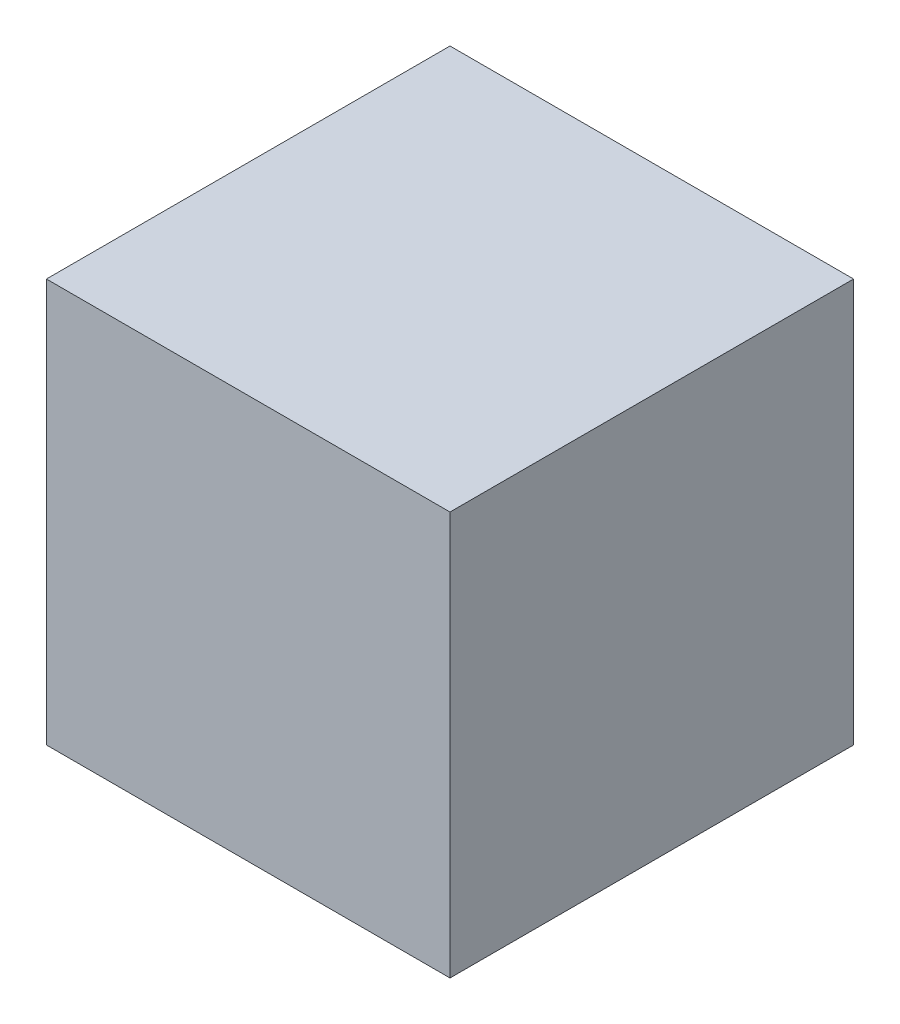
SolidWorks part; units mm, degrees
ref_plane "Front Plane" through (0, 0, 0) normal (0, 0, 1) x (1, 0, 0)
ref_plane "Top Plane" through (0, 0, 0) normal (0, 1, 0) x (1, 0, 0)
ref_plane "Right Plane" through (0, 0, 0) normal (1, 0, 0) x (0, 0, -1)
sketch "Sketch1" plane through (0, 0, 0) normal (0, 1, 0) x (1, 0, 0)
  line L1 (-115, -115) -> (115, -115)
  line L2 (-115, -115) -> (-115, 115)
  line L3 (-115, 115) -> (115, 115)
  line L4 (115, -115) -> (115, 115)
  line L5 (-115, -115) -> (115, 115) construction
  line L6 (-115, 115) -> (115, -115) construction
  point P0 (0, 0)
  dimension "D1" = 230
extrude "Boss-Extrude1" add sketch "Sketch1" along normal blind 230
